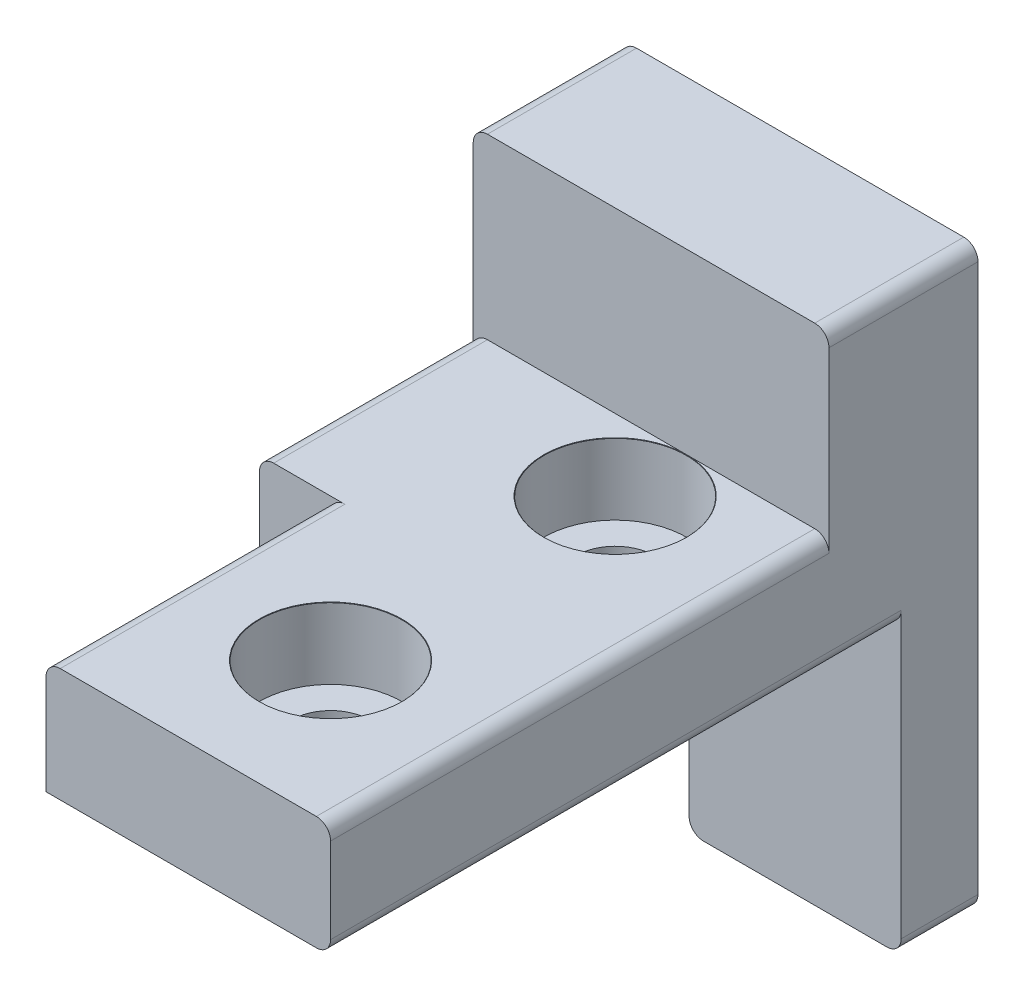
SolidWorks part; units mm, degrees
ref_plane "Front Plane" through (0, 0, 0) normal (0, 0, 1) x (1, 0, 0)
ref_plane "Top Plane" through (0, 0, 0) normal (0, 1, 0) x (1, 0, 0)
ref_plane "Right Plane" through (0, 0, 0) normal (1, 0, 0) x (0, 0, -1)
sketch "Sketch1" plane through (0, 0, 0) normal (0, 1, 0) x (1, 0, 0)
  line L0 (-10, 0) -> (-15, 0)
  line L1 (-10, -20) -> (10, -20)
  line L2 (-10, -20) -> (-10, 0)
  line L3 (-10, 20) -> (10, 20)
  line L4 (10, -20) -> (10, 20)
  line L5 (-10, -20) -> (10, 20) construction
  line L6 (-10, 20) -> (10, -20) construction
  line L7 (-15, 0) -> (-15, 20)
  line L8 (-15, 20) -> (-10, 20)
  point P0 (0, 0)
  point P8 (0, 0)
  point P10 (0, 0)
  dimension "D1" = 20
  dimension "D2" = 40
  dimension "D3" = 20
  dimension "D4" = 5
extrude "Boss-Extrude1" add sketch "Sketch1" along normal blind 8
sketch "Sketch2" plane through (0, 8, 0) normal (0, 1, 0) x (1, 0, 0)
  line L0 (0, -20) -> (0, 20) construction
  line L1 (-10, -20) -> (10, -20) construction
  line L2 (10, 20) -> (-15, 20) construction
  line L3 (-15, 10) -> (10, 10) construction
  line L4 (-15, 20) -> (-15, 0) construction
  line L5 (10, -20) -> (10, 20) construction
  point P14 (0, 10)
  point P15 (0, -10)
  point P16 (0, 0)
  dimension "D2" = 20
hole_wizard "CBORE for M5 SHCS1" positions "Sketch3" profile "Sketch4" counterbore size "M5" standard "ANSI Metric" end condition through all
sketch "Sketch3" plane through (0, 8, 0) normal (0, 1, 0) x (1, 0, 0)
  point P3 (0, 10)
  point P6 (0, -10)
sketch "Sketch4" plane through (0, 8, -10) normal (1, 0, 0) x (0, 0, 1)
  line L0 (0, 0) -> (0, 8)
  line L1 (0, 8) -> (2.75, 8)
  line L3 (2.75, 8) -> (2.75, 5)
  line L4 (5, 5) -> (2.75, 5)
  line L5 (5, 5) -> (5, 0.025)
  line L6 (5, 0.025) -> (5.025, 0)
  line L7 (5.025, 0) -> (0, 0)
  line L8 (-5, 0.025) -> (-5.025, 0) construction
  line L11 (0, -6.35) -> (0, 107.95) construction
  dimension "Thru Hole Dia." = 5.5
  dimension "Thru Hole Depth" = 8
  dimension "C'Bore Dia." = 10
  dimension "C'Bore Depth" = 5
  dimension "Near C'Sink Dia." = 10.05
  dimension "Near C'Sink Angle" = 90
sketch "Sketch5" plane through (0, 8, 0) normal (0, 1, 0) x (1, 0, 0)
  line L0 (10, -20) -> (10, 20) construction
  line L1 (-15, 18) -> (10, 18)
  line L2 (-15, 18) -> (-15, 15.025)
  line L3 (-15, 15.025) -> (10, 15.025)
  line L4 (10, 18) -> (10, 15.025)
  line L5 (10, 20) -> (-15, 20) construction
  line L6 (-15, 20) -> (-15, 0) construction
  circle A0 centre (0, 10) radius 5.025 construction
  dimension "D1" = 2
extrude "Boss-Extrude2" add sketch "Sketch5" along normal blind 12.51
sketch "Sketch6" plane through (0, 0, -18) normal (0, 0, -1) x (-1, 0, 0)
  line L0 (15, 20.51) -> (15, 8) construction
  line L1 (-10, 20.51) -> (15, 20.51)
  line L2 (-10, 20.51) -> (-10, 20)
  line L3 (-5, 17.51) -> (15, 17.51)
  line L4 (15, 20.51) -> (15, 17.51)
  line L5 (-5, 17.51) -> (-5, 8)
  line L6 (15, 8) -> (-10, 8) construction
  line L7 (-5, 8) -> (-10, 8)
  line L8 (-10, 8) -> (-10, 20)
  line L9 (15, 16.01) -> (12, 16.01)
  line L10 (12, 16.01) -> (12, 8)
  line L11 (-10, 8) -> (15, 8) construction
  line L12 (12, 8) -> (15, 8)
  line L13 (15, 8) -> (15, 16.01)
  dimension "D1" = 3
  dimension "D2" = 3
  dimension "D3" = 1.5
  dimension "D4" = 5
extrude "Boss-Extrude3" add sketch "Sketch6" along normal blind 7.5
sketch "Sketch7" plane through (0, 0, -20) normal (0, 0, -1) x (-1, 0, 0)
  line L6 (-10, 0) -> (15, 0)
  line L7 (15, 0) -> (15, 8)
  line L8 (15, 8) -> (12, 8)
  line L9 (12, 8) -> (-5, 8)
  line L10 (-5, 8) -> (-10, 8)
  line L11 (-10, 8) -> (-10, 0)
  line L12 (-10, 0) -> (15, 0)
  line L13 (15, 0) -> (15, 8)
  line L14 (15, 8) -> (12, 8)
  line L15 (12, 8) -> (-5, 8)
  line L16 (-5, 8) -> (-10, 8)
  line L17 (-10, 8) -> (-10, 0)
  dimension "D1" = 0
extrude "Boss-Extrude4" add sketch "Sketch7" along normal up to surface (5.5 mm away) up to face at (0, 15.34, -25.5)
sketch "Sketch8" plane through (0, 0, -18) normal (0, 0, -1) x (-1, 0, 0)
  line L0 (12, 16.01) -> (12, 8) construction
  line L1 (-5, 8) -> (12, 8)
  line L2 (-5, 8) -> (-5, 9.25)
  line L3 (-5, 9.25) -> (12, 9.25)
  line L4 (12, 8) -> (12, 9.25)
  dimension "D1" = 1.25
extrude "Boss-Extrude5" add sketch "Sketch8" along normal up to surface (7.5 mm away) up to face at (-5.4, 12.406, -25.5)
sketch "Sketch9" plane through (0, 0, -25.5) normal (0, 0, -1) x (-1, 0, 0)
  line L0 (-10, 0) -> (15, 0)
  line L1 (15, 0) -> (15, -5.4)
  line L2 (15, -5.4) -> (4.9, -5.4)
  line L3 (4.9, -5.4) -> (4.9, -20)
  line L4 (4.9, -20) -> (-10, -20)
  line L5 (-10, -20) -> (-10, 0)
  dimension "D1" = 5.4
  dimension "D2" = 10.1
  dimension "D3" = 20
extrude "Boss-Extrude6" add sketch "Sketch9" against normal blind 5.4
fillet "Fillet2" radius 1 10 edges at (-15, 0, -10.05) (10, 0, -0.05) (-10, 8, 10) (-15, 8, -7.5125) (10, 8, 2.4875) (-15, 20.51, -20.2625) (10, 20.51, -20.2625) (-15, -5.4, -22.8) (-4.9, -20, -22.8) (10, -20, -22.8)
